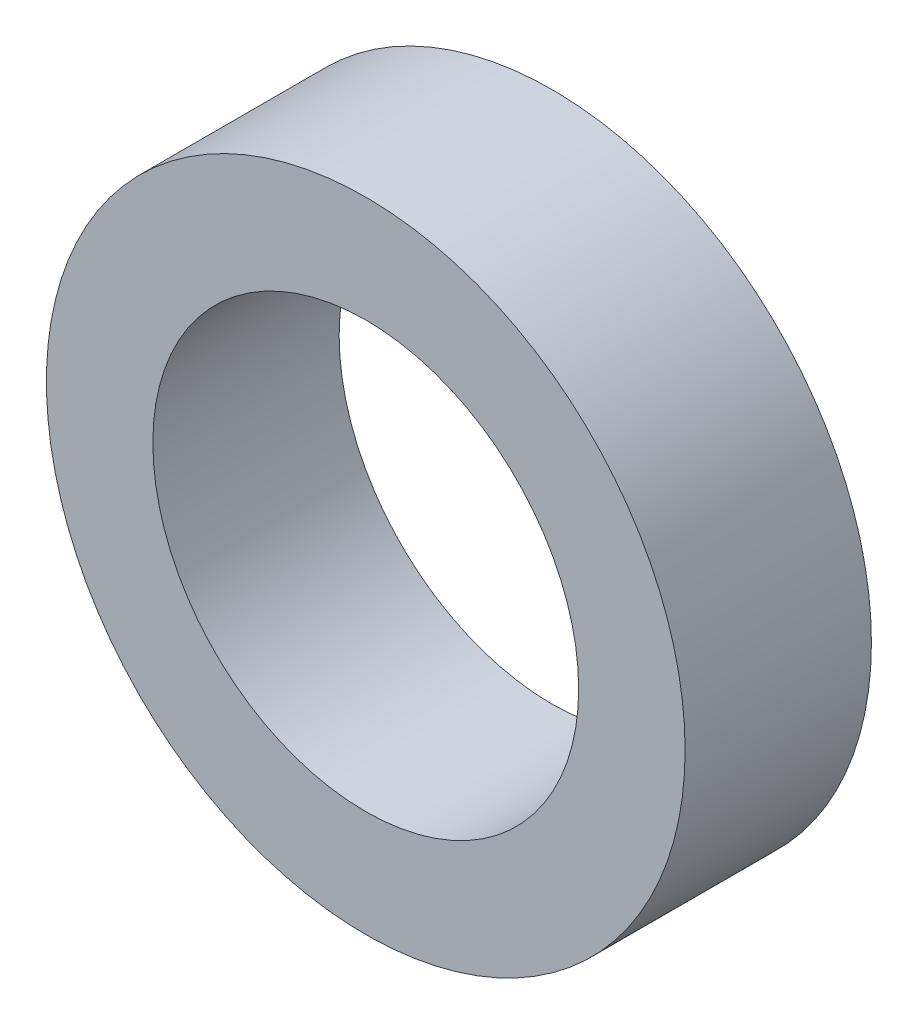
SolidWorks part; units mm, degrees
ref_plane "前视基准面" through (0, 0, 0) normal (0, 0, 1) x (1, 0, 0)
ref_plane "上视基准面" through (0, 0, 0) normal (0, 1, 0) x (1, 0, 0)
ref_plane "右视基准面" through (0, 0, 0) normal (1, 0, 0) x (0, 0, -1)
sketch "草图1" plane through (0, 0, 0) normal (0, 0, 1) x (1, 0, 0)
  circle A1 centre (0, 0) radius 4
  circle A2 centre (0, 0) radius 6
extrude "凸台-拉伸1" add sketch "草图1" along normal blind 3.5 contours A2
extrude "切除-拉伸2" cut sketch "草图1<8>" along normal blind 3.5 contours A1
sketch "草图1<8>" plane through (0, 0, 0) normal (0, 0, 1) x (1, 0, 0) same geometry as "草图1"
